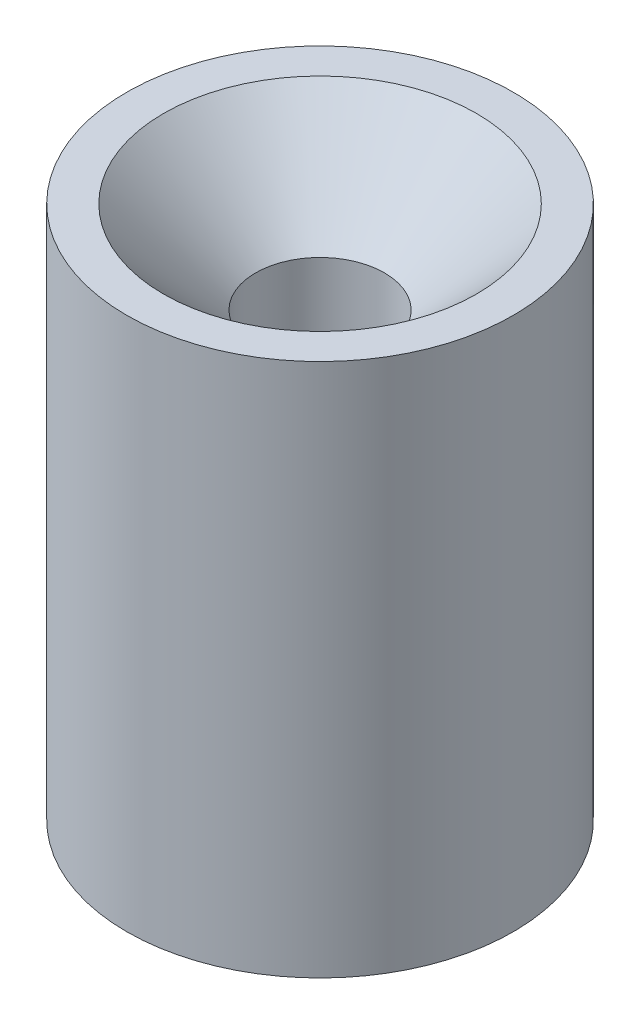
SolidWorks part; units mm, degrees
material "1060-O (SS)"
ref_plane "Front Plane" through (0, 0, 0) normal (0, 0, 1) x (1, 0, 0)
ref_plane "Top Plane" through (0, 0, 0) normal (0, 1, 0) x (1, 0, 0)
ref_plane "Right Plane" through (0, 0, 0) normal (1, 0, 0) x (0, 0, -1)
sketch "Sketch1" plane through (0, 0, 0) normal (0, 1, 0) x (1, 0, 0)
  circle A0 centre (0, 0) radius 21
  dimension "D1" = 42
extrude "Boss-Extrude1" add sketch "Sketch1" along normal blind 24 and the other way blind 24
sketch "Sketch3" plane through (0, 0, 0) normal (0, 1, 0) x (1, 0, 0)
  circle A0 centre (0, 0) radius 7
  dimension "D1" = 14
extrude "Cut-Extrude1" cut sketch "Sketch3" against normal up to next (24 mm away) draft 15 and the other way up to next (24 mm away) draft outward yes
sketch "Sketch4" plane through (0, 24, 0) normal (0, 1, 0) x (1, 0, 0)
  circle A1 centre (0, 0) radius 21
extrude "Boss-Extrude2" add sketch "Sketch4" along normal blind 10
sketch "Sketch5" plane through (0, 24, 0) normal (0, -1, 0) x (1, 0, 0)
  circle A0 centre (0, 0) radius 7
extrude "Cut-Extrude2" cut sketch "Sketch5" against normal up to next (10 mm away) draft 45 draft outward yes
